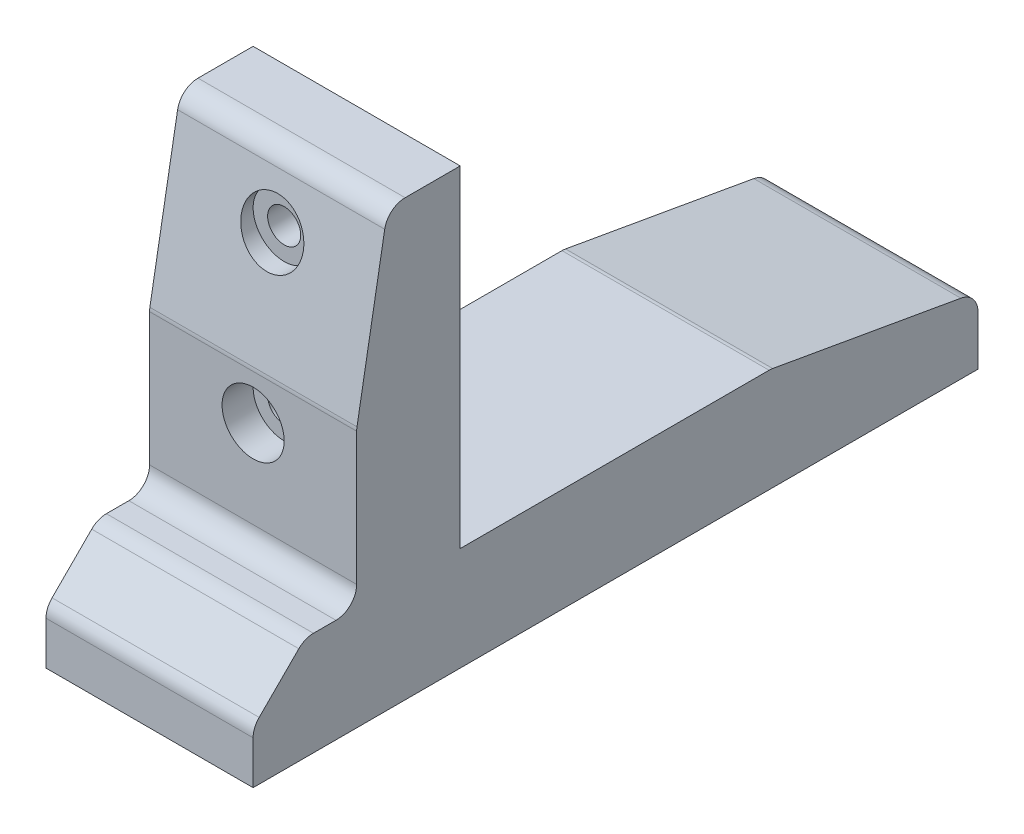
SolidWorks part; units mm, degrees
ref_plane "Front Plane" through (0, 0, 0) normal (0, 0, 1) x (1, 0, 0)
ref_plane "Top Plane" through (0, 0, 0) normal (0, 1, 0) x (1, 0, 0)
ref_plane "Right Plane" through (0, 0, 0) normal (1, 0, 0) x (0, 0, -1)
ref_plane "Plane1" through (47.5, 0, 0) normal (1, 0, 0) x (0, 0, -1)
sketch "Sketch3" plane through (47.5, 0, 0) normal (1, 0, 0) x (0, 0, -1)
  line L0 (0, -27) -> (0, 103) construction
  line L1 (0, -15.5) -> (-10, -15.5)
  line L2 (0, -15.5) -> (0, -47.5)
  line L3 (0, -47.5) -> (-10, -47.5)
  line L4 (-10, -15.5) -> (-10, -47.5)
  line L5 (15, -47) -> (0, -47) construction
  line L6 (-20, -57.5) -> (50, -57.5)
  line L7 (-20, -57.5) -> (-20, -47.5)
  line L8 (-20, -47.5) -> (50, -47.5)
  line L9 (50, -57.5) -> (50, -47.5)
  point P10 (19.0104, -51.4536)
  point P11 (0, -51.4536)
  dimension "D1" = 0.5
  dimension "D2" = 10
  dimension "D3" = 32
  dimension "D4" = 50
  dimension "D5" = 10
  dimension "D6" = 10
extrude "Boss-Extrude1" add sketch "Sketch3" along normal mid plane 20 contours L6 L9 L8 L3 L7 | L1 L4 L3 L2 region at (47.5, -31.5, 5) region at (47.5, -52.5, -15)
sketch "Sketch4" plane through (0, 0, 0) normal (0, 0, -1) x (-1, 0, 0)
  circle A0 centre (-47.5, -37) radius 1.6 construction
  circle A1 centre (-47.5, -22) radius 1.6 construction
  circle A2 centre (-47.5, -37) radius 1.6
  circle A3 centre (-47.5, -22) radius 1.6
  circle A4 centre (-47.5, -22) radius 3
  circle A5 centre (-47.5, -37) radius 3
  dimension "D1" = 6
extrude "Cut-Extrude1" cut sketch "Sketch4" against normal through all contours A3 | A2 region at (47.5, -37, 0) region at (47.5, -22, 0)
extrude "Cut-Extrude2" cut sketch "Sketch4<3>" along normal blind 3 from surface contours A4 A3 | A5 A2 region at (50.4151, -22, 0) region at (50.4151, -37, 0) starting at face at (47.5, -20.4, 10)
sketch "Sketch4<3>" plane through (0, 0, 0) normal (0, 0, -1) x (-1, 0, 0) same geometry as "Sketch4"
chamfer "Chamfer1" distance 20 angle 10 1 edges at (47.5, -47.5, -50) first distance on face at (47.5, -47.5, -25)
chamfer "Chamfer2" distance 5 angle 45 1 edges at (47.5, -47.5, 20)
chamfer "Chamfer3" distance 3 angle 80 1 edges at (47.5, -15.5, 10) first distance on face at (47.5, -15.5, 5)
fillet "Fillet1" radius 2 7 edges at (47.5, -15.5, 7) (47.5, -32.5138, 10) (47.5, -47.5, 10) (47.5, -47.5, 15) (47.5, -52.5, 20) (47.5, -47.5, -30) (47.5, -51.0265, -50)
